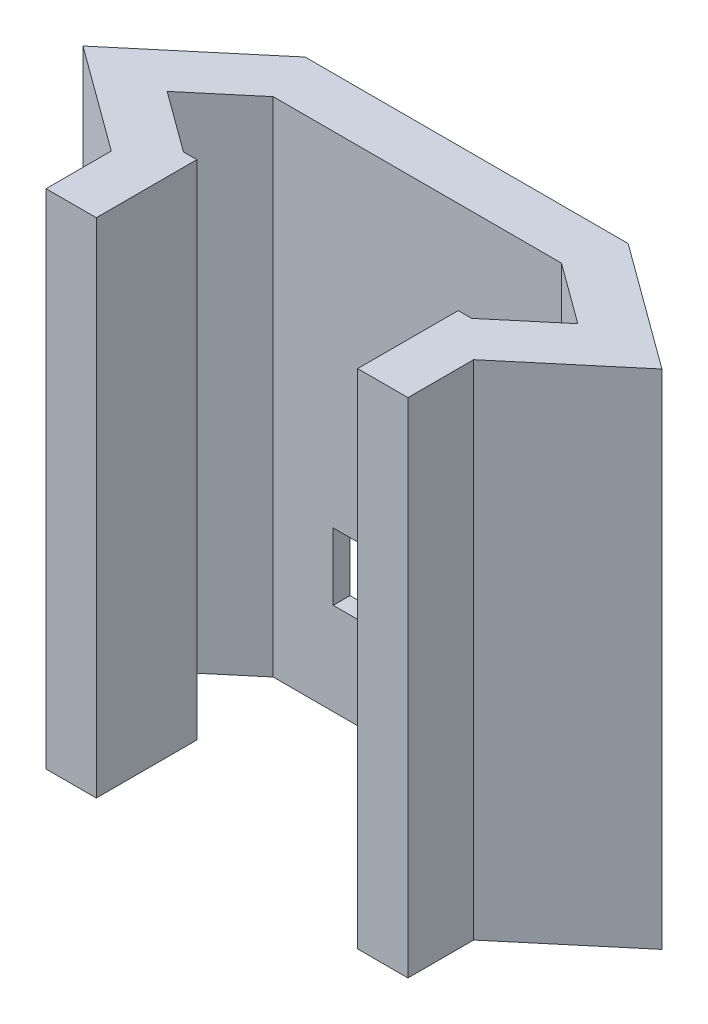
SolidWorks part; units mm, degrees
ref_plane "Front Plane" through (0, 0, 0) normal (0, 0, 1) x (1, 0, 0)
ref_plane "Top Plane" through (0, 0, 0) normal (0, 1, 0) x (1, 0, 0)
ref_plane "Right Plane" through (0, 0, 0) normal (1, 0, 0) x (0, 0, -1)
sketch "Sketch1" plane through (0, 0, 0) normal (0, 1, 0) x (1, 0, 0)
  line L9 (-5.8527, 1.9534) -> (11.3547, 1.9534)
  line L15 (11.3547, 1.9534) -> (14.972, -0.6901)
  line L16 (14.972, -0.6901) -> (11.5352, -3.5821)
  line L17 (11.5352, -3.5821) -> (10.7257, -3.5821)
  line L18 (10.7257, -3.5821) -> (10.7257, -6.5821)
  line L19 (-4.8743, -6.5821) -> (10.7257, -6.5821)
  line L20 (-4.8743, -3.5821) -> (-4.8743, -6.5821)
  line L21 (-4.8743, -3.5821) -> (-5.6722, -3.5821)
  line L22 (-5.6722, -3.5821) -> (-9.2895, -0.9387)
  line L23 (-9.2895, -0.9387) -> (-5.8527, 1.9534)
  line L24 (-6.947, 4.9534) -> (12.334, 4.9534)
  line L25 (12.334, 4.9534) -> (19.829, -0.5238)
  line L26 (19.829, -0.5238) -> (13.7257, -5.6596)
  line L27 (13.7257, -5.6596) -> (13.7257, -5.6596)
  line L28 (13.7257, -5.6596) -> (13.7257, -9.5821)
  line L29 (-7.8743, -9.5821) -> (13.7257, -9.5821)
  line L30 (-7.8743, -5.6886) -> (-7.8743, -9.5821)
  line L31 (-7.8743, -5.6886) -> (-7.8743, -5.6886)
  line L32 (-7.8743, -5.6886) -> (-14.1466, -1.105)
  line L33 (-14.1466, -1.105) -> (-6.947, 4.9534)
  line L34 (-4.8743, -6.5821) -> (-4.8743, -9.5821)
  line L35 (10.7257, -6.5821) -> (10.7257, -9.5821)
  dimension "D1" = 3
extrude "Boss-Extrude2" add sketch "Sketch1" along normal blind 30 contours L18 L35 L29 L28 L27 L26 L25 L24 L33 L32 L31 L30 L34 L20 L21 L22 L23 L9 L15 L16 L17 region at (-7.8091, 0, -0.7901)
sketch "Sketch21" plane through (0, 0, -4.9534) normal (0, 0, -1) x (-1, 0, 0)
  line L3 (-12.7318, 3.5) -> (7.2682, 3.5)
  line L4 (-12.7318, 3.5) -> (-12.7318, 26.5)
  line L5 (-12.7318, 26.5) -> (7.2682, 26.5)
  line L6 (7.2682, 3.5) -> (7.2682, 26.5)
  point P8 (-2.7318, 15)
  dimension "D1" = 23
  dimension "D2" = 20
extrude "Cut-Extrude18" cut sketch "Sketch21" against normal blind 2
sketch "Sketch22" plane through (0, 0, -2.9534) normal (0, 0, -1) x (-1, 0, 0)
  line L0 (-12.7318, 3.5) -> (7.2682, 3.5) construction
  line L1 (-7.7318, 9.5) -> (2.2682, 9.5)
  line L2 (-7.7318, 9.5) -> (-7.7318, 5.5)
  line L3 (-7.7318, 5.5) -> (2.2682, 5.5)
  line L4 (2.2682, 9.5) -> (2.2682, 5.5)
  line L5 (7.2682, 26.5) -> (-12.7318, 26.5) construction
  line L6 (-2.7318, 26.5) -> (-2.7318, 9.5) construction
  dimension "D1" = 2
  dimension "D2" = 10
  dimension "D3" = 4
extrude "Cut-Extrude19" cut sketch "Sketch22" against normal through all
